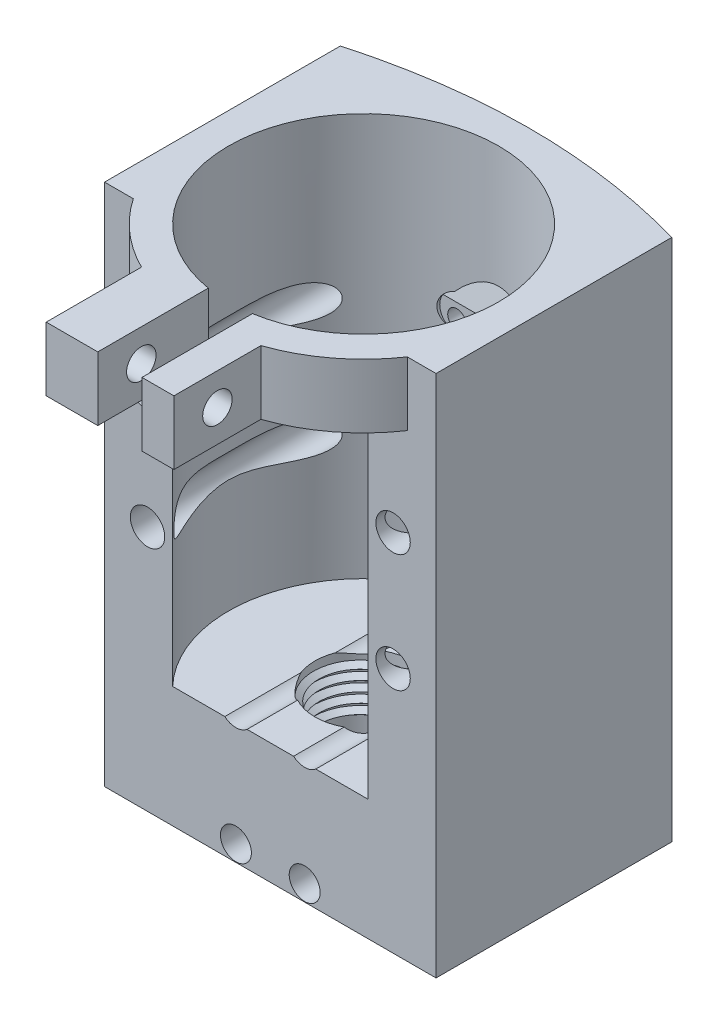
SolidWorks part; units mm, degrees
material "Alliage 1060"
ref_plane "Plan de face" through (0, 0, 0) normal (0, 0, 1) x (1, 0, 0)
ref_plane "Plan de dessus" through (0, 0, 0) normal (0, 1, 0) x (1, 0, 0)
ref_plane "Plan de droite" through (0, 0, 0) normal (1, 0, 0) x (0, 0, -1)
sketch "Plaque vissé" plane through (0, 0, 0) normal (0, 0, 1) x (1, 0, 0)
  line L0 (0, 18.5312) -> (0, -61.6688) construction
  line L1 (-31, 18.5312) -> (31, 18.5312)
  line L3 (-31, -61.6688) -> (31, -61.6688)
  line L6 (31, 18.5312) -> (33.75, 18.5312)
  line L7 (33.75, 18.5312) -> (33.75, -61.6688)
  line L8 (33.75, -61.6688) -> (31, -61.6688)
  line L9 (-31, 18.5312) -> (-33.75, 18.5312)
  line L10 (-33.75, 18.5312) -> (-33.75, -61.6688)
  line L11 (-33.75, -61.6688) -> (-31, -61.6688)
  circle A0 centre (-25, 11.6011) radius 1.875
  circle A1 centre (-7, 11.6011) radius 1.875
  circle A2 centre (-25, -12.3989) radius 1.875
  circle A3 centre (-7, -12.3989) radius 1.875
  circle A4 centre (7, 11.6011) radius 1.875
  circle A5 centre (25, 11.6011) radius 1.875
  circle A6 centre (25, -12.3989) radius 1.875
  circle A7 centre (7, -12.3989) radius 1.875
  circle A8 centre (-7, -34.3989) radius 1.875
  circle A9 centre (7, -34.3989) radius 1.875
  circle A10 centre (-7, -58.3989) radius 1.875
  circle A11 centre (7, -58.3989) radius 1.875
  circle A12 centre (-17, -33.3989) radius 3.5
  circle A13 centre (17, -33.3989) radius 3.5
  dimension "D3" = 3.75
  dimension "D2" = 3.75
  dimension "D9" = 3.75
  dimension "D11" = 3.75
  dimension "D12" = 3.75
  dimension "D14" = 3.75
  dimension "D20" = 7
  dimension "D22" = 7
  dimension "D24" = 26.75
  dimension "D25" = 26.75
  dimension "D1" = 62
  dimension "D4" = 24
  dimension "D5" = 18
  dimension "D6" = 14
  dimension "D7" = 2.75
  dimension "D8" = 2.75
  dimension "D10" = 22
  dimension "D13" = 24
  dimension "D15" = 24
  dimension "D16" = 24
  dimension "D17" = 22
  dimension "D18" = 14
  dimension "D19" = 14
  dimension "D21" = 1
  dimension "D23" = 10
  dimension "D26" = 10
  dimension "D27" = 80.2
extrude "Boss.-Extru.1" add sketch "Plaque vissé" along normal blind 3 contours L0 L1 L3 A3 A2 A1 A0 | L1 L0 L3 A7 A5 A4 A6 region at (16.9718, -21.5425, 0) region at (-16.9718, -21.5425, 0)
sketch "Def plan filetage plateau" plane through (0, 0, 0) normal (0, 0, 1) x (1, 0, 0)
  line L0 (-25, 11.6011) -> (-25, -92.8989) construction
  line L1 (-25, 11.6011) -> (-25, -44.3989) construction
  dimension "D1" = 104.5
  dimension "D2" = 56
ref_plane "Filetage" through (0, -61.6688, 0) normal (0, -1, 0) x (-1, 0, 0)
sketch "esquisse filetage" plane through (0, -61.6688, 0) normal (0, -1, 0) x (-1, 0, 0)
  line L2 (33.75, 0) -> (-33.75, 0) construction
  line L3 (33.75, -48) -> (-33.75, -48)
  line L4 (33.75, -3) -> (33.75, -48)
  line L5 (33.75, -3) -> (-33.75, -3)
  line L6 (-33.75, -3) -> (-33.75, -48)
  circle A0 centre (0, -29) radius 9.9
  point P8 (-33.75, -25.5)
  point P16 (0, -48)
  dimension "D2" = 19.8
  dimension "D3" = 48
  dimension "D1" = 29
extrude "Boss.-Extru.4" add sketch "esquisse filetage" against normal blind 24.6 separate body
extrude "Enlèv. mat.-Extru.6" cut sketch "Plaque vissé<6>" along normal up to surface (48 mm away) contours A11 | A10 region at (7, -58.3989, 0) up to face at (0, -49.3688, 48)
sketch "Plaque vissé<6>" plane through (0, 0, 0) normal (0, 0, 1) x (1, 0, 0) same geometry as "Plaque vissé"
ref_plane "Plan4" through (0, 44.9312, 0) normal (0, 1, 0) x (1, 0, 0)
sketch "Esquisse13" plane through (0, -55, 43.1) normal (-1, 0, 0) x (0, 0, -1)
  line L0 (24, -16.1412) -> (22.88, -16.9512)
  line L1 (22.88, -16.9512) -> (24, -17.7612)
  line L2 (24, -17.7612) -> (24, -16.1412)
  line L4 (4.2, -17.9312) -> (24, -17.9312) construction
  dimension "D1" = 1.62
  dimension "D2" = 1.12
  dimension "D3" = 0.98
sketch "Esquisse14" plane through (0, 44.9312, 0) normal (0, 1, 0) x (1, 0, 0)
  line L0 (-33.75, -48) -> (-33.75, -3) construction
  line L1 (-4.5, -56.1293) -> (-4.5, -78.6293)
  line L2 (-4.5, -78.6293) -> (-11, -78.6293)
  line L3 (-11, -78.6293) -> (-11, -60.9071)
  line L4 (4.5, -56.1293) -> (4.5, -78.6293)
  line L5 (4.5, -78.6293) -> (11, -78.6293)
  line L6 (11, -78.6293) -> (11, -60.9071)
  arc A1 (4.5, -56.1293) -> (-4.5, -56.1293) centre (0, -29) ccw
  arc A2 (11, -60.9071) -> (-11, -60.9071) centre (0, -29) ccw
  arc A3 (5.5227, -62.2951) -> (-5.5227, -62.2951) centre (0, -29) ccw construction
  arc A4 (4.5, -56.1293) -> (-4.5, -56.1293) centre (0, -29) ccw construction
  circle A5 centre (0, -29) radius 9.9 construction
  dimension "D1" = 27.5
  dimension "D2" = 9
  dimension "D5" = 22.5
  dimension "D3" = 6.5
  dimension "D4" = 6.5
extrude "Boss.-Extru.8" add sketch "Esquisse14" against normal blind 13 separate body
sketch "Esquisse15" plane through (-11, 0, 0) normal (-1, 0, 0) x (0, 0, 1)
  line L0 (60.9071, 44.9312) -> (78.6293, 31.9312) construction
  line L2 (66.8815, 43.4312) -> (63.9947, 38.4312)
  line L3 (63.9947, 38.4312) -> (66.8815, 33.4312)
  line L4 (66.8815, 33.4312) -> (72.655, 33.4312)
  line L5 (72.655, 33.4312) -> (75.5417, 38.4312)
  line L6 (75.5417, 38.4312) -> (72.655, 43.4312)
  line L7 (72.655, 43.4312) -> (66.8815, 43.4312)
  line L8 (78.6293, 44.9312) -> (78.6293, 31.9312)
  line L14 (78.6293, 31.9312) -> (54.1529, 31.9312)
  line L15 (-4.75, 31.9312) -> (60.9071, 31.9312) construction
  line L16 (54.1529, 31.9312) -> (54.1529, 44.9312)
  line L17 (60.9071, 44.9312) -> (-4.75, 44.9312) construction
  line L18 (54.1529, 44.9312) -> (78.6293, 44.9312)
  line L19 (60.9071, 31.9312) -> (60.9071, 44.9312)
  circle A0 centre (69.7682, 38.4312) radius 3
  circle A1 centre (69.7682, 38.4312) radius 5 construction
  line M4 (60.9071, 44.9312) -> (60.9071, 31.9312)
  dimension "D1" = 6
  dimension "D2" = 10
extrude "Enlèv. mat.-Extru.1" cut sketch "Esquisse15" against normal up to surface (22 mm away) contours A0 region at (-11, 38.4312, 69.7682) up to face at (11, 38.4312, 69.7682)
extrude "Boss.-Extru.9" add sketch "Esquisse15<4>" along normal blind 4 contours L7 L6 L5 L4 L3 L2 | L16 L18 L14 | L18 L16 L14 M4 region at (-11, 38.4312, 78.4095) region at (-11, 38.4312, 57.53)
sketch "Esquisse15<4>" plane through (-11, 0, 0) normal (-1, 0, 0) x (0, 0, 1) same geometry as "Esquisse15"
sketch "Esquisse16" plane through (0, 18.5312, 0) normal (0, 1, 0) x (1, 0, 0)
  line L0 (33.75, -3) -> (8.9582, -3)
  line L1 (-33.75, 0) -> (33.75, 0)
  line L2 (-33.75, 0) -> (-33.75, -3)
  line L4 (33.75, 0) -> (33.75, -3)
  line L5 (-33.75, -3) -> (33.75, -3) construction
  line L6 (-8.9582, -3) -> (-33.75, -3)
  arc A1 (-8.9582, -3) -> (8.9582, -3) centre (0, -29) cw
  arc A2 (11, -60.9071) -> (-15, -59.2335) centre (0, -29) ccw construction
  arc A3 (-11, -54.2042) -> (-4.5, -56.1293) centre (0, -29) ccw construction
  spline S0 degree 2 poles (33.75, 0) (0.0865, 9.5) (-33.75, 0) knots 0 0 0 1 1 1
  line M1 (33.75, 0) -> (-33.75, 0)
  line M2 (-33.75, 0) -> (-33.75, -3)
  line M3 (-33.75, -3) -> (33.75, -3)
  line M4 (33.75, -3) -> (33.75, 0)
ref_plane "Plan3" through (0, -38.8588, 0) normal (0, 1, 0) x (1, 0, 0)
sketch "Esquisse26" plane through (0, -38.8588, 0) normal (0, 1, 0) x (1, 0, 0)
  circle A1 centre (0, -29) radius 9.9
  circle A4 centre (0, -29) radius 9.9 construction
curve "Hélice/Spirale1" pitch 2 height 10.6 radius 9.9 centre (0, -38.8588, 29) axis (0, -1, 0) start towards (0, 0, -1)
sweep "Balayage1" add profiles "Esquisse13" path "Hélice/Spirale1"
extrude "Boss.-Extru.22" add sketch "Esquisse16" along normal up to surface (26.4 mm away) contours A1 M1 M3 M4 | S0 A1 M1 | A1 L1 M3 | A1 M3 M1 M2 | A1 L1 region at (0, 18.5312, 1.4122) region at (0, 18.5312, 2.3986) region at (0.0173, 18.5312, -1.9) up to face at (-2.7497, 44.9312, 53.7685)
sketch "Esquisse28" plane through (0, 44.9312, 0) normal (0, 1, 0) x (1, 0, 0)
  circle A0 centre (0, -29) radius 27.5
extrude "Enlèv. mat.-Extru.8" cut sketch "Esquisse28" against normal blind 24
sketch "Esquisse29" plane through (0, -37.0688, 0) normal (0, 1, 0) x (1, 0, 0)
  line L0 (33.75, -48) -> (-33.75, -48) construction
  line L1 (33.75, -3) -> (33.75, -48) construction
  line L2 (21.5189, -3) -> (33.75, -3) construction
  line L7 (33.75, -3) -> (33.75, -48)
  line L18 (19.8809, -48) -> (33.75, -48)
  line L19 (33.75, -3) -> (8.9582, -3)
  arc A4 (4.5, -56.1293) -> (-4.5, -56.1293) centre (0, -29) ccw construction
  arc A8 (8.9582, -3) -> (19.8809, -48) centre (0, -29) cw
extrude "Boss.-Extru.28" add sketch "Esquisse29" along normal up to surface (82 mm away) up to face at (1.9594, 44.9312, 36.3668)
mirror "Symétrie1" about plane through (0, 0, 0) normal (1, 0, 0) of "Boss.-Extru.28"
sketch "Esquisse23" plane through (0, 0, 3) normal (0, 0, 1) x (1, 0, 0)
  circle A0 centre (25, 12.5) radius 3.5
  circle A1 centre (7, 12.5) radius 3.5
  circle A2 centre (-7, 12.5) radius 3.5
  circle A3 centre (-25, 12.5) radius 3.5
  circle A4 centre (25, -11.5) radius 3.5
  circle A5 centre (7, -11.5) radius 3.5
  circle A6 centre (-7, -11.5) radius 3.5
  circle A7 centre (-25, -11.5) radius 3.5
  circle A8 centre (-7, -34.3989) radius 3.5
  circle A10 centre (7, -58.3989) radius 3.15
  circle A11 centre (-7, -58.3989) radius 3.15
  circle A12 centre (7, -34.3989) radius 3.5
  dimension "D1" = 7
  dimension "D2" = 7
  dimension "D3" = 7
  dimension "D4" = 7
  dimension "D5" = 7
  dimension "D6" = 7
  dimension "D7" = 7
  dimension "D8" = 7
  dimension "D9" = 6.3
  dimension "D10" = 6.3
  dimension "D11" = 7
  dimension "D12" = 7
extrude "Enlèv. mat.-Extru.7" cut sketch "Esquisse23" along normal through all
chamfer "Chanfrein4" distance 1.7 angle 75 1 edges at (0, 20.9312, 3) first distance on face at (0, 20.9312, 2.25)
